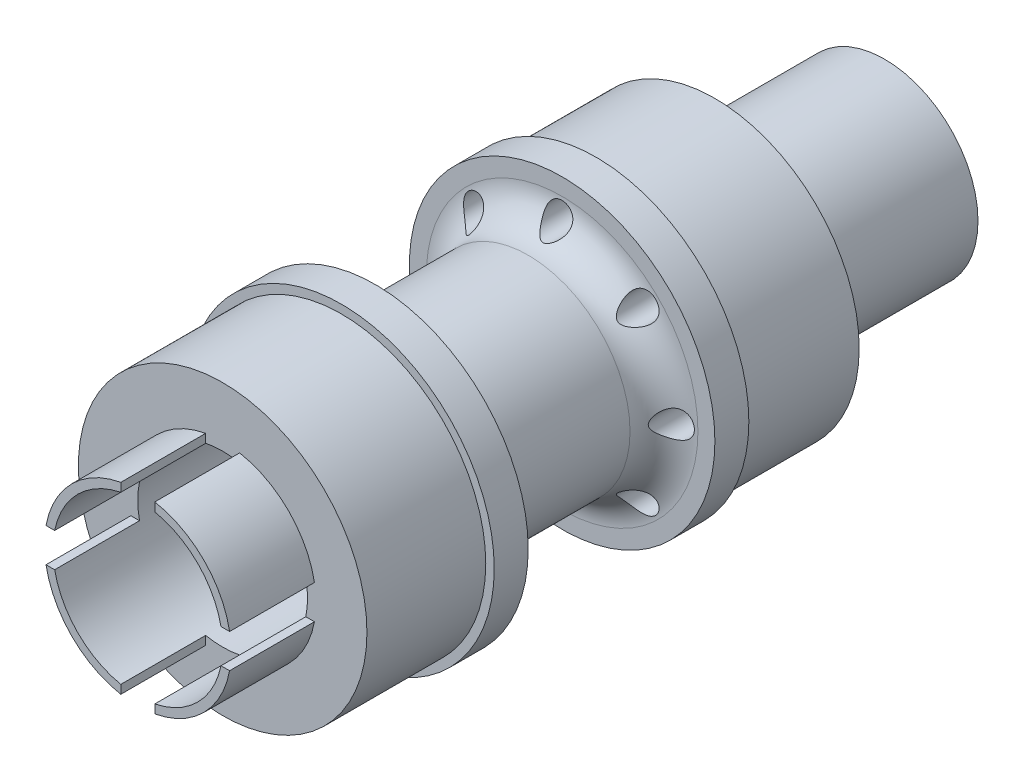
SolidWorks part; units mm, degrees
material "Alliage 1060"
ref_plane "Plan de face" through (0, 0, 0) normal (0, 0, 1) x (1, 0, 0)
ref_plane "Plan de dessus" through (0, 0, 0) normal (0, 1, 0) x (1, 0, 0)
ref_plane "Plan de droite" through (0, 0, 0) normal (1, 0, 0) x (0, 0, -1)
sketch "Esquisse1" plane through (0, 0, 0) normal (0, 0, 1) x (1, 0, 0)
  circle A0 centre (0, 0) radius 4.5
  circle A1 centre (0, 0) radius 5.5
  dimension "D1" = 9
  dimension "D2" = 11
extrude "Boss.-Extru.1" add sketch "Esquisse1" along normal blind 10
sketch "Esquisse3" plane through (0, 0, 10) normal (0, 0, 1) x (1, 0, 0)
  circle A0 centre (0, 0) radius 8.5
  circle A1 centre (0, 0) radius 5
  dimension "D1" = 10
  dimension "D2" = 17
extrude "Boss.-Extru.3" add sketch "Esquisse3" along normal blind 7
sketch "Esquisse4" plane through (0, 0, 17) normal (0, 0, 1) x (1, 0, 0)
  circle A0 centre (0, 0) radius 5
  circle A1 centre (0, 0) radius 9
  dimension "D1" = 10
  dimension "D2" = 18
extrude "Boss.-Extru.4" add sketch "Esquisse4" along normal blind 2
sketch "Esquisse7" plane through (0, 0, 19) normal (0, 0, 1) x (1, 0, 0)
  circle A0 centre (0, 0) radius 5
  circle A1 centre (0, 0) radius 6
  dimension "D1" = 10
  dimension "D2" = 12
extrude "Boss.-Extru.7" add sketch "Esquisse7" along normal blind 11
sketch "Esquisse8" plane through (0, 0, 30) normal (0, 0, 1) x (1, 0, 0)
  circle A0 centre (0, 0) radius 5
  circle A1 centre (0, 0) radius 9
  dimension "D1" = 10
  dimension "D2" = 18
extrude "Boss.-Extru.8" add sketch "Esquisse8" along normal blind 2
sketch "Esquisse15" plane through (0, 0, 32) normal (0, 0, 1) x (1, 0, 0)
  circle A0 centre (0, 0) radius 5
  circle A1 centre (0, 0) radius 8.5
  dimension "D1" = 10
  dimension "D2" = 17
extrude "Boss.-Extru.9" add sketch "Esquisse15" along normal blind 7
sketch "Esquisse16" plane through (0, 0, 39) normal (0, 0, 1) x (1, 0, 0)
  circle A0 centre (0, 0) radius 5
  circle A1 centre (0, 0) radius 5.5
  dimension "D1" = 10
  dimension "D2" = 11
extrude "Boss.-Extru.10" add sketch "Esquisse16" along normal blind 5
sketch "Esquisse17" plane through (0, 0, 44) normal (0, 0, 1) x (1, 0, 0)
  line L1 (-10, 1) -> (10, 1)
  line L2 (-10, 1) -> (-10, -1)
  line L3 (-10, -1) -> (10, -1)
  line L4 (10, 1) -> (10, -1)
  line L5 (-1, -10) -> (1, -10)
  line L6 (-1, -10) -> (-1, 10)
  line L7 (-1, 10) -> (1, 10)
  line L8 (1, -10) -> (1, 10)
  dimension "D1" = 2
  dimension "D2" = 1
  dimension "D3" = 10
  dimension "D4" = 20
  dimension "D5" = 2
  dimension "D6" = 20
  dimension "D7" = 10
  dimension "D8" = 1
extrude "Enlèv. mat.-Extru.1" cut sketch "Esquisse17" against normal blind 5 contours L6 L7 L8 L5 | L1 L4 L3 L2
hole_wizard "Trou pour taraudage pour trou taraudé M21" positions "Esquisse21" profile "Esquisse22" hole size "M2" standard "ISO" end condition up to next
sketch "Esquisse21" plane through (0, 0, 10) normal (0, 0, -1) x (-1, 0, 0)
  point P0 (-7, 0)
  point P11 (-4.9497, 4.9497)
  point P12 (0, 7)
  point P13 (4.9497, 4.9497)
  point P14 (7, 0)
  point P15 (4.9497, -4.9497)
  point P16 (0, -7)
  point P17 (-4.9497, -4.9497)
  point P18 (0, 0)
  dimension "D1" = 7
  dimension "D2" = 8
sketch "Esquisse22" plane through (7, 0, 10) normal (1, 0, 0) x (0, 1, 0)
  line L0 (0, 0) -> (0, 9)
  line L1 (0, 9) -> (0.8, 9)
  line L2 (0.8, 9) -> (0.8, 0)
  line L5 (0.8, 0) -> (0, 0)
  line L11 (0, -6.35) -> (0, 107.95) construction
  dimension "Diamètre du perçage jusqu'au prochain" = 1.6
  dimension "Profondeur du perçage jusqu'au prochain" = 9
fillet "Congé1" radius 2 2 edges at (6, 0, 19) (6, 0, 30)
